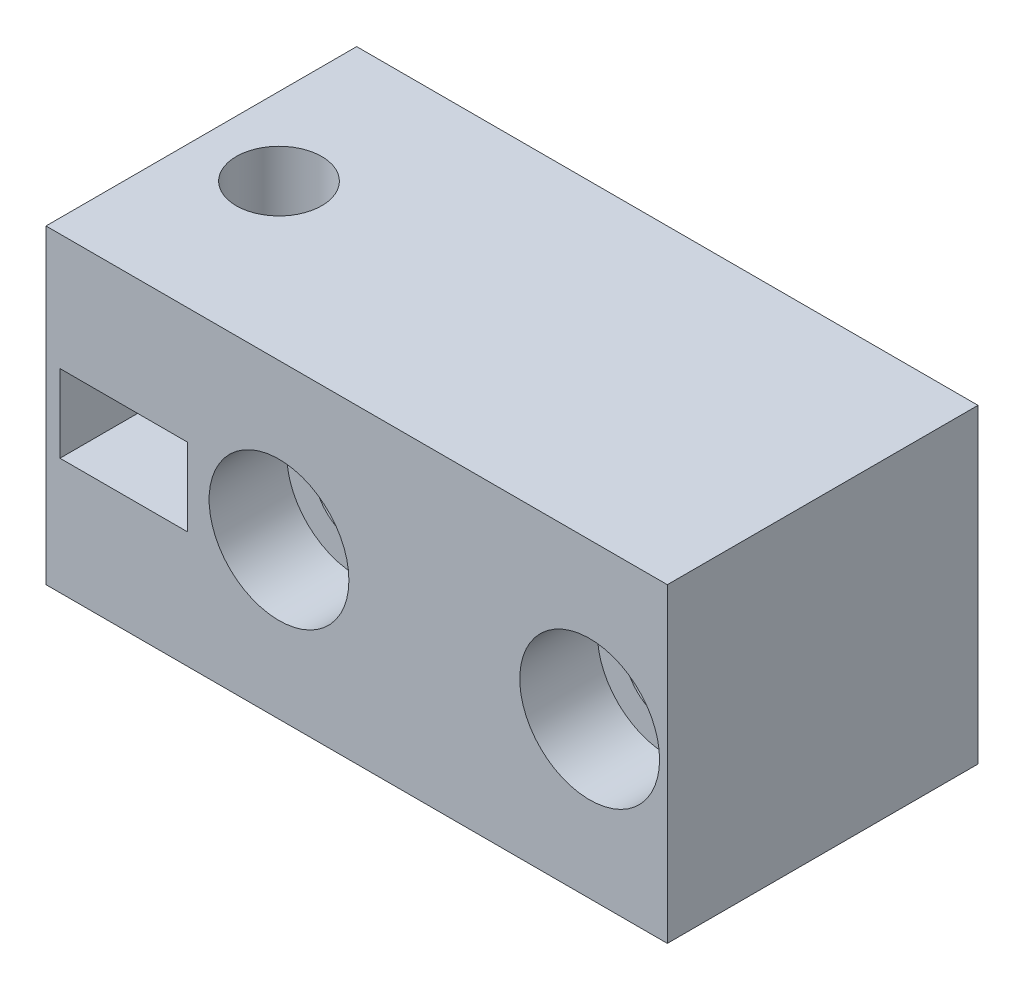
SolidWorks part; units mm, degrees
ref_plane "Front Plane" through (0, 0, 0) normal (0, 0, 1) x (1, 0, 0)
ref_plane "Top Plane" through (0, 0, 0) normal (0, 1, 0) x (1, 0, 0)
ref_plane "Right Plane" through (0, 0, 0) normal (1, 0, 0) x (0, 0, -1)
sketch "Sketch1" plane through (0, 0, 0) normal (0, 0, 1) x (1, 0, 0)
  line L1 (0, 0) -> (50, 0)
  line L2 (0, 0) -> (0, 20)
  line L3 (0, 20) -> (50, 20)
  line L4 (50, 0) -> (50, 20)
  dimension "D1" = 20
  dimension "D2" = 50
extrude "Boss-Extrude1" add sketch "Sketch1" along normal blind 20
sketch "Sketch2" plane through (0, 0, 20) normal (0, 0, 1) x (1, 0, 0)
  line L0 (50, 20) -> (0, 20) construction
  line L1 (0, 20) -> (0, 0) construction
  line L2 (50, 0) -> (50, 20) construction
  line L4 (10.9, 7.5) -> (19.1, 7.5)
  line L5 (10.9, 7.5) -> (10.9, 12.5)
  line L6 (10.9, 12.5) -> (19.1, 12.5)
  line L7 (19.1, 7.5) -> (19.1, 12.5)
  circle A0 centre (25, 10) radius 2.75
  circle A1 centre (45, 10) radius 2.75
  dimension "D1" = 5.5
  dimension "D2" = 5.5
  dimension "D3" = 10
  dimension "D4" = 10
  dimension "D5" = 25
  dimension "D6" = 5
  dimension "D7" = 5
  dimension "D8" = 8.2
  dimension "D9" = 10.9
  dimension "D10" = 7.5
extrude "Cut-Extrude1" cut sketch "Sketch2" against normal through all
sketch "Sketch3" plane through (0, 20, 0) normal (0, 1, 0) x (1, 0, 0)
  line L0 (0, -20) -> (0, 0) construction
  line L1 (50, 0) -> (0, 0) construction
  circle A0 centre (15, -10) radius 2.75
  dimension "D1" = 5.5
  dimension "D2" = 15
  dimension "D3" = 10
extrude "Cut-Extrude2" cut sketch "Sketch3" against normal through all
sketch "Sketch4" plane through (0, 7.5, 0) normal (0, 1, 0) x (1, 0, 0)
  line L0 (19.1, -7.5) -> (15.1, -5.1339)
  line L1 (19.1, 0) -> (19.1, -20) construction
  line L2 (15.1, -5.1339) -> (10.9, -7.5)
  line L3 (10.9, 0) -> (10.9, -20) construction
  line L8 (10.9, -20) -> (19.1, -20)
  line L9 (19.1, -20) -> (19.1, 0)
  line L10 (19.1, 0) -> (10.9, 0)
  line L11 (10.9, 0) -> (10.9, -20)
  line L13 (19.1, -7.5) -> (19.1, 0)
  line L14 (19.1, 0) -> (10.9, 0)
  line L15 (10.9, 0) -> (10.9, -7.5)
  point P4 (10.9, -10)
  point P9 (19.1, -10)
  dimension "D1" = 2.5
  dimension "D2" = 2.5
  dimension "D3" = 120
  dimension "D4" = 4
  dimension "D5" = 0
extrude "Boss-Extrude2" add sketch "Sketch4" along normal up to next
sketch "Sketch5" plane through (0, 0, 0) normal (0, 0, -1) x (-1, 0, 0)
  line L0 (-50, 20) -> (0, 20) construction
  line L1 (-39, 7) -> (-31, 7)
  line L2 (-39, 7) -> (-39, 13)
  line L3 (-39, 13) -> (-31, 13)
  line L4 (-31, 7) -> (-31, 13)
  line L5 (-50, 0) -> (-50, 20) construction
  dimension "D1" = 6
  dimension "D2" = 8
  dimension "D3" = 7
  dimension "D4" = 11
extrude "Boss-Extrude3" add sketch "Sketch5" along normal blind 3
sketch "Sketch6" plane through (0, 0, 20) normal (0, 0, 1) x (1, 0, 0)
  circle A0 centre (25, 10) radius 4.5
  circle A1 centre (45, 10) radius 4.5
  dimension "D1" = 9
  dimension "D2" = 9
extrude "Cut-Extrude3" cut sketch "Sketch6" against normal blind 5
sketch "Sketch7" plane through (0, 0, 20) normal (0, 0, 1) x (1, 0, 0)
  line L0 (0, 0) -> (50, 0) construction
  line L1 (0, 20) -> (10, 20)
  line L2 (0, 20) -> (0, 0)
  line L3 (0, 0) -> (10, 0)
  line L4 (10, 20) -> (10, 0)
  dimension "D1" = 10
extrude "Cut-Extrude4" cut sketch "Sketch7" against normal through all
